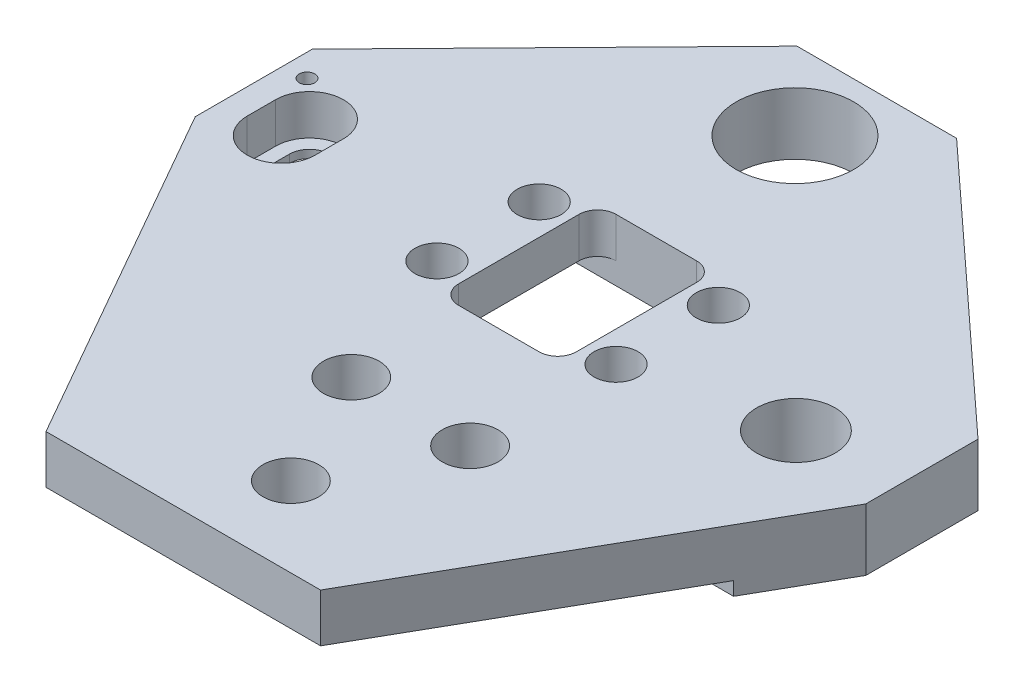
SolidWorks part; units mm, degrees
material "1060 Alloy"
ref_plane "Front Plane" through (0, 0, 0) normal (0, 0, 1) x (1, 0, 0)
ref_plane "Top Plane" through (0, 0, 0) normal (0, 1, 0) x (1, 0, 0)
ref_plane "Right Plane" through (0, 0, 0) normal (1, 0, 0) x (0, 0, -1)
sketch "Sketch1" plane through (0, 0, 0) normal (0, 1, 0) x (1, 0, 0)
  line L0 (0, 0) -> (0, -56.0308) construction
  line L1 (0, 0) -> (54.1, 0) construction
  line L2 (54.1, 18.1) -> (54.1, 0)
  line L3 (54.1, 18.1) -> (10.3345, 58.4092)
  line L4 (10.3345, 58.4092) -> (-15.4155, 58.4092)
  line L5 (-15.4155, 58.4092) -> (-54.1, 18.8922)
  line L6 (-54.1, 18.8922) -> (-54.1, 0)
  line L7 (-54.1, 0) -> (-22.15, -56.0308)
  line L8 (-22.15, -56.0308) -> (22.15, -56.0308)
  line L9 (22.15, -56.0308) -> (54.1, 0)
  line L11 (-9.5, 20.3092) -> (9.5, 20.3092)
  line L12 (-9.5, 20.3092) -> (-9.5, -5.1108)
  line L13 (-9.5, -5.1108) -> (9.5, -5.1108)
  line L14 (9.5, 20.3092) -> (9.5, -5.1108)
  dimension "D1" = 108.2
  dimension "D2" = 50.92
  dimension "D3" = 25.75
  dimension "D4" = 64.5
  dimension "D5" = 18.1
  dimension "D6" = 59.5
  dimension "D7" = 44.3
  dimension "D8" = 55.3
  dimension "D9" = 38.1
  dimension "D10" = 19
  dimension "D11" = 44.6
  dimension "D12" = 25.42
extrude "Boss-Extrude2" add sketch "Sketch1" along normal blind 10
fillet "Fillet1" radius 3 4 edges at (-9.5, 5, 5.1108) (9.5, 5, 5.1108) (9.5, 5, -20.3092) (-9.5, 5, -20.3092)
sketch "Sketch3" plane through (0, 0, -58.4092) normal (0, 0, -1) x (-1, 0, 0)
  line L0 (-10.3345, 0) -> (15.4155, 0) construction
  line L1 (54.1, 0) -> (35, 0)
  line L2 (54.1, 0) -> (54.1, 2.2)
  line L3 (54.1, 2.2) -> (35, 2.2)
  line L4 (35, 0) -> (35, 2.2)
  line L5 (54.1, 10) -> (54.1, 0) construction
  line L6 (-10.3345, 10) -> (15.4155, 10) construction
  dimension "D1" = 7.8
  dimension "D2" = 19.1
extrude "Cut-Extrude2" cut sketch "Sketch3" against normal through all
sketch "Sketch4" plane through (0, 10, 0) normal (0, 1, 0) x (1, 0, 0)
  line L0 (0, 20.3092) -> (0, -5.1108) construction
  line L1 (6.5, 20.3092) -> (-6.5, 20.3092) construction
  line L2 (-6.5, -5.1108) -> (6.5, -5.1108) construction
  line L3 (-14.45, 7.5992) -> (14.45, 7.5992) construction
  line L4 (-44.53, 8.8692) -> (-44.53, 4.2892) construction
  line L5 (-39.06, 8.8692) -> (-39.06, 4.2892)
  line L6 (-50, 8.8692) -> (-50, 4.2892)
  line L7 (4.48, -43.1508) -> (4.48, -31.1076) construction
  line L8 (-5.105, -23.8162) -> (4.48, -31.1076) construction
  line L9 (-5.105, -23.8162) -> (4.48, -43.1508) construction
  line L10 (-5.105, -23.8162) -> (14.065, -23.8162) construction
  line L11 (57.39, 62.1092) -> (57.39, -55.0587) construction
  line L12 (-3.065, 45.7342) -> (6.41, 45.7342) construction
  line L13 (9.5, -2.1108) -> (9.5, 17.3092) construction
  line L14 (-3.065, 45.7342) -> (-3.065, 55.2092) construction
  line L16 (-3.065, 36.2592) -> (-3.065, 20.3092) construction
  line L19 (38.2, 4.6192) -> (44.53, 4.6192) construction
  line L21 (57.39, 62.1092) -> (-64.0899, 62.1092) construction
  line L22 (38.2, 4.6192) -> (38.2, 10.9492) construction
  line L23 (-44.53, 14.3392) -> (-44.53, -1.1808) construction
  line L24 (-14.45, -0.6508) -> (-14.45, 15.8492) construction
  line L25 (14.45, -0.6508) -> (14.45, 15.8492) construction
  circle A0 centre (38.2, 4.6192) radius 6.33
  circle A1 centre (-14.45, -0.6508) radius 3.55
  circle A2 centre (-14.45, 15.8492) radius 3.55
  circle A3 centre (14.45, -0.6508) radius 3.55
  circle A4 centre (14.45, 15.8492) radius 3.55
  circle A5 centre (-5.105, -23.8162) radius 4.5
  circle A6 centre (14.065, -23.8162) radius 4.5
  circle A7 centre (4.48, -43.1508) radius 4.5
  circle A8 centre (4.48, -31.1076) radius 1.875
  arc A9 (-39.06, 8.8692) -> (-50, 8.8692) centre (-44.53, 8.8692) ccw
  arc A10 (-50, 4.2892) -> (-39.06, 4.2892) centre (-44.53, 4.2892) ccw
  circle A11 centre (-3.065, 45.7342) radius 9.475
  circle A12 centre (-50.45, 14.3792) radius 1.25
  point P28 (-44.53, 6.5792)
  dimension "D1" = 9
  dimension "D5" = 12.66
  dimension "D10" = 18.95
  dimension "D18" = 3.75
  dimension "D21" = 7.1
  dimension "D22" = 2.5
  dimension "D2" = 19.17
  dimension "D3" = 21.58
  dimension "D4" = 38.04
  dimension "D6" = 28.7
  dimension "D7" = 47.89
  dimension "D8" = 52.91
  dimension "D9" = 50.98
  dimension "D11" = 15.95
  dimension "D12" = 6.9
  dimension "D13" = 51.16
  dimension "D14" = 10.94
  dimension "D15" = 59.5
  dimension "D16" = 15.52
  dimension "D17" = 47.77
  dimension "D19" = 28.9
  dimension "D20" = 16.5
  dimension "D23" = 59.95
  dimension "D24" = 7.8
extrude "Cut-Extrude3" cut sketch "Sketch4" against normal through all contours A11 | A6 | A5 | A7 | A0 | A4 | A3 | A1 | A2 | A12 region at (38.2, 10, -4.6192) region at (-14.45, 10, 0.6508) region at (-14.45, 10, -15.8492) region at (14.45, 10, 0.6508) region at (14.45, 10, -15.8492) region at (-5.105, 10, 23.8162) region at (14.065, 10, 23.8162) region at (4.48, 10, 43.1508) region at (-3.065, 10, -45.7342) region at (-50.45, 10, -14.3792)
sketch "Sketch5" plane through (-35, 0, 0) normal (-1, 0, 0) x (0, 0, 1)
  line L0 (33.4957, 2.2) -> (-38.4032, 2.2) construction
  line L1 (13.5908, 2.2) -> (56.0308, 2.2)
  line L2 (13.5908, 2.2) -> (13.5908, 0)
  line L3 (13.5908, 0) -> (56.0308, 0)
  line L4 (56.0308, 2.2) -> (56.0308, 0)
  line L5 (-58.4092, 10) -> (-58.4092, 0) construction
  line L6 (33.4957, 0) -> (-38.4032, 0) construction
  line L7 (56.0308, 10) -> (56.0308, 0) construction
  dimension "D1" = 72
extrude "Cut-Extrude4" cut sketch "Sketch5" against normal through all
sketch "Sketch6" plane through (0, 0, 0) normal (0, -1, 0) x (1, 0, 0)
  line L0 (-6.5, 5.1108) -> (6.5, 5.1108) construction
  line L1 (19.695, -20.3092) -> (-19.695, -20.3092)
  line L2 (19.695, -20.3092) -> (19.695, 5.1108)
  line L3 (19.695, 5.1108) -> (-19.695, 5.1108)
  line L4 (-19.695, -20.3092) -> (-19.695, 5.1108)
  line L5 (6.5, -20.3092) -> (-6.5, -20.3092) construction
  line L6 (0, 5.1108) -> (0, -20.3092) construction
  line L7 (9.5, 2.1108) -> (9.5, -17.3092) construction
  line L8 (-9.5, -17.3092) -> (-9.5, 2.1108) construction
  dimension "D1" = 39.39
extrude "Cut-Extrude5" cut sketch "Sketch6" against normal blind 3.5
fillet "Fillet2" radius 2 4 edges at (19.695, 1.75, 5.1108) (19.695, 1.75, -20.3092) (-19.695, 1.75, 5.1108) (-19.695, 1.75, -20.3092)
extrude "Cut-Extrude6" cut sketch "Sketch4<3>" against normal blind 6.5 contours L6 A10 L5 A9 region at (-44.53, 10, -6.5792)
sketch "Sketch4<3>" plane through (0, 10, 0) normal (0, 1, 0) x (1, 0, 0) same geometry as "Sketch4"
sketch "Sketch7" plane through (0, 3.5, 0) normal (0, 1, 0) x (-1, 0, 0)
  line L0 (44.53, -8.8692) -> (44.53, -4.2892) construction
  line L1 (41.28, -8.8692) -> (41.28, -4.2892)
  line L2 (47.78, -8.8692) -> (47.78, -4.2892)
  arc A0 (41.28, -8.8692) -> (47.78, -8.8692) centre (44.53, -8.8692) ccw
  arc A1 (47.78, -4.2892) -> (41.28, -4.2892) centre (44.53, -4.2892) ccw
  arc A2 (39.06, -8.8692) -> (50, -8.8692) centre (44.53, -8.8692) ccw construction
  arc A3 (50, -4.2892) -> (39.06, -4.2892) centre (44.53, -4.2892) ccw construction
  point P2 (44.53, -6.5792)
  dimension "D1" = 6.5
extrude "Cut-Extrude7" cut sketch "Sketch7" against normal through all
